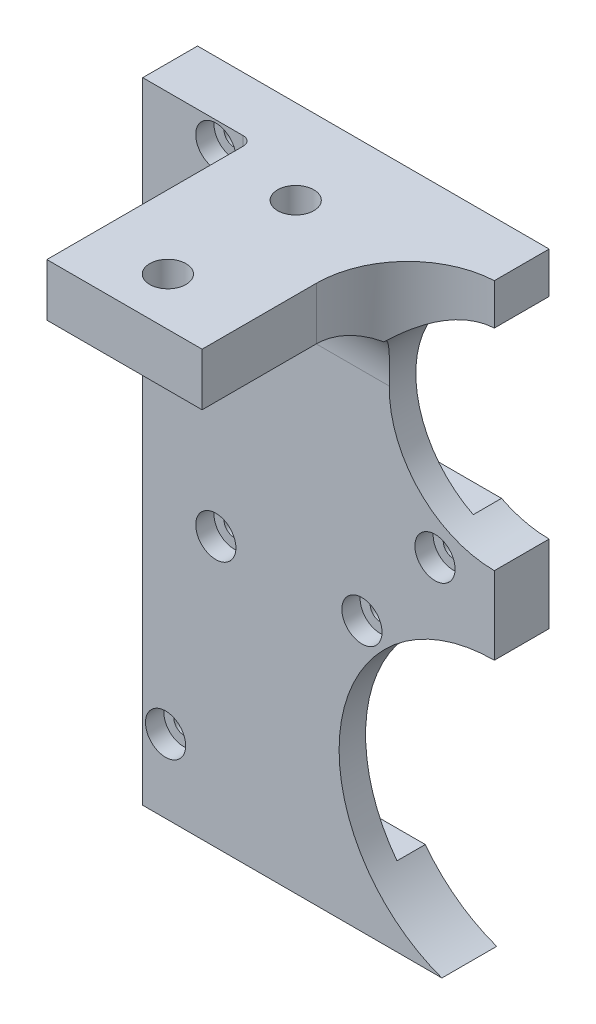
SolidWorks part; units mm, degrees
ref_plane "Front Plane" through (0, 0, 0) normal (0, 0, 1) x (1, 0, 0)
ref_plane "Top Plane" through (0, 0, 0) normal (0, 1, 0) x (1, 0, 0)
ref_plane "Right Plane" through (0, 0, 0) normal (1, 0, 0) x (0, 0, -1)
sketch "Sketch1" plane through (0, 0, 0) normal (0, 0, 1) x (1, 0, 0)
  line L0 (19.25, 16) -> (19.25, 11.5)
  line L1 (-19.25, 16) -> (19.25, 16)
  line L2 (-19.25, 16) -> (-19.25, -16)
  line L3 (-19.25, -16) -> (19.25, -16) construction
  line L4 (19.25, 16) -> (19.25, -16) construction
  line L5 (-19.25, 16) -> (19.25, -16) construction
  line L6 (-19.25, -16) -> (19.25, 16) construction
  line L7 (19.25, -11.5) -> (19.25, -16)
  line L8 (-19.25, 0) -> (19.25, 0) construction
  line L9 (19.25, -21) -> (19.25, -20) construction
  line L10 (-19.25, -21) -> (19.25, -21) construction
  line L11 (-19.25, -21) -> (-19.25, -53)
  line L12 (-19.25, -53) -> (19.25, -53) construction
  line L13 (19.25, -54) -> (19.25, -53) construction
  line L14 (19.25, -21) -> (19.25, -53) construction
  line L15 (-19.25, -21) -> (19.25, -53) construction
  line L16 (-19.25, -53) -> (19.25, -21) construction
  line L17 (-19.25, -37) -> (19.25, -37) construction
  line L18 (-19.25, -16) -> (-19.25, -21)
  line L19 (19.25, -16) -> (19.25, -21) construction
  line L20 (-19.25, -53) -> (13.5054, -53)
  line L21 (19.25, -16) -> (19.25, -20)
  arc A0 (19.25, 11.5) -> (19.25, -11.5) centre (19.25, 0) ccw
  circle A1 centre (12.75, 13.5) radius 1.1 construction
  circle A2 centre (4.75, 13.5) radius 1.1 construction
  circle A3 centre (-3.25, 13.5) radius 1.1 construction
  circle A4 centre (-11.25, 13.5) radius 1.1
  circle A5 centre (-11.25, -13.5) radius 1.1 construction
  circle A6 centre (-3.25, -13.5) radius 1.1 construction
  circle A7 centre (4.75, -13.5) radius 1.1 construction
  circle A8 centre (12.75, -13.5) radius 1.1
  circle A9 centre (-16.75, 8) radius 1.1 construction
  circle A10 centre (-16.75, -8) radius 1.1
  arc A11 (19.25, -20) -> (19.25, -54) centre (19.25, -37) ccw construction
  circle A12 centre (12.75, -23.5) radius 1.1 construction
  circle A13 centre (4.75, -23.5) radius 1.1
  circle A14 centre (-3.25, -23.5) radius 1.1 construction
  circle A15 centre (-11.25, -23.5) radius 1.1
  circle A16 centre (-11.25, -50.5) radius 1.1 construction
  circle A17 centre (-3.25, -50.5) radius 1.1 construction
  circle A18 centre (4.75, -50.5) radius 1.1 construction
  circle A19 centre (12.75, -50.5) radius 1.1 construction
  circle A20 centre (-16.75, -29) radius 1.1 construction
  circle A21 centre (-16.75, -45) radius 1.1
  arc A22 (13.5054, -53) -> (19.25, -20) centre (19.25, -37) cw
  point P0 (0, 0)
  dimension "D3" = 23
  dimension "D5" = 2.2
  dimension "D11" = 17
  dimension "D13" = 8
  dimension "D1" = 32
  dimension "D2" = 38.5
  dimension "D4" = 6.5
  dimension "D6" = 8
  dimension "D7" = 8
  dimension "-" = 8
  dimension "D8" = 27
  dimension "D9" = 36
  dimension "D10" = 16
  dimension "D12" = 37
  dimension "D14" = 8
  dimension "D15" = 8
  dimension "D16" = 6.5
  dimension "D17" = 27
  dimension "D18" = 16
extrude "Boss-Extrude1" add sketch "Sketch1" along normal blind 6
ref_plane "Plane1" through (0, 0, 3.1) normal (0, 0, 1) x (1, 0, 0)
sketch "Sketch2" plane through (0, 0, 3.1) normal (0, 0, 1) x (1, 0, 0)
  line L0 (19.25, 11.5) -> (19.25, 16) construction
  line L1 (19.25, 10.25) -> (-13.45, 10.25)
  line L2 (19.25, 10.25) -> (19.25, -10.25)
  line L3 (19.25, -10.25) -> (-13.45, -10.25)
  line L4 (-13.45, 10.25) -> (-13.45, -10.25)
  line L5 (0, 0) -> (19.25, 0) construction
  line L6 (-19.25, -18.5) -> (19.25, -18.5) construction
  line L7 (-19.25, 16) -> (-19.25, -53) construction
  line L9 (19.25, -26.75) -> (-13.45, -26.75)
  line L10 (19.25, -47.25) -> (19.25, -26.75)
  line L11 (19.25, -47.25) -> (-13.45, -47.25)
  line L12 (-13.45, -47.25) -> (-13.45, -26.75)
  dimension "D1" = 20.5
  dimension "D2" = 32.7
extrude "Cut-Extrude1" cut sketch "Sketch2" against normal through all
hole_wizard "CBORE for M2 SHCS1" positions "Sketch8" profile "Sketch7" counterbore size "M2" standard "Ansi Metric" end condition through all
sketch "Sketch8" plane through (0, 0, 6) normal (0, 0, 1) x (1, 0, 0)
  point P10 (12.75, -13.5)
  point P22 (-11.25, -23.5)
  point P28 (4.75, -23.5)
  point P34 (-16.75, -45)
  point P48 (-16.75, -8)
  point P51 (-11.25, 13.5)
sketch "Sketch7" plane through (12.75, -13.5, 6) normal (1, 0, 0) x (0, -1, 0)
  line L0 (0, 0) -> (0, 6)
  line L1 (0, 6) -> (1.05, 6)
  line L3 (1.05, 6) -> (1.05, 2)
  line L4 (1.05, 2) -> (2.2, 2)
  line L5 (2.2, 2) -> (2.2, 0)
  line L7 (2.2, 0) -> (0, 0)
  line L11 (0, -6.35) -> (0, 107.95) construction
  dimension "Thru Hole Dia." = 2.1
  dimension "Thru Hole Depth" = 6
  dimension "C'Bore Dia." = 4.4
  dimension "C'Bore Depth" = 2
sketch "Sketch9" plane through (0, 0, 0) normal (0, 0, -1) x (-1, 0, 0)
  line L0 (-19.25, 16) -> (19.25, 16) construction
  line L1 (7.25, 16) -> (-9.75, 16)
  line L2 (7.25, 16) -> (7.25, 10.25)
  line L3 (7.25, 10.25) -> (-9.75, 10.25)
  line L4 (-9.75, 16) -> (-9.75, 10.25)
  line L6 (-14.0358, 10.25) -> (13.45, 10.25) construction
  line L7 (19.25, 16) -> (19.25, -53) construction
  dimension "D1" = 17
  dimension "D2" = 12
extrude "Boss-Extrude3" add sketch "Sketch9" against normal blind 28.5
sketch "Sketch10" plane through (0, 16, 0) normal (0, 1, 0) x (1, 0, 0)
  line L1 (-7.25, -28.5) -> (-7.25, -6) construction
  line L2 (0.75, -9.25) -> (0.75, -23.25) construction
  line L3 (0.75, -16.25) -> (5.25, -16.25) construction
  line L4 (19.25, 0) -> (-19.25, 0) construction
  circle A0 centre (0.75, -9.25) radius 1.9844
  circle A2 centre (0.75, -23.25) radius 1.9844
  point P3 (0, 0)
  dimension "D5" = 3.9688
  dimension "D1" = 16.25
  dimension "D2" = 14
  dimension "D3" = 8
  dimension "D4" = 4.5
extrude "Cut-Extrude2" cut sketch "Sketch10" against normal blind 8
fillet "Fillet1" radius 10 1 edges at (1.25, 10.25, 6)
fillet "Fillet2" radius 10 1 edges at (9.75, 11.2404, 6)
fillet "Fillet3" radius 1 1 edges at (-7.25, 8.125, 6)
